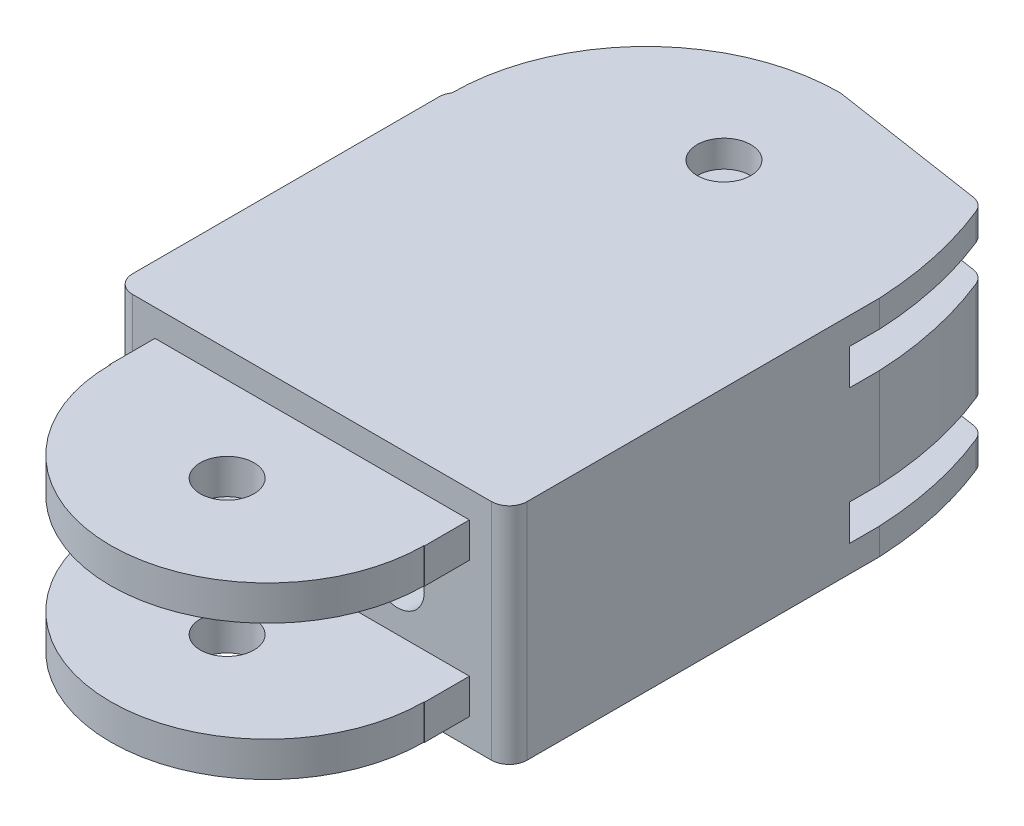
SolidWorks part; units mm, degrees
ref_plane "Front Plane" through (0, 0, 0) normal (0, 0, 1) x (1, 0, 0)
ref_plane "Top Plane" through (0, 0, 0) normal (0, 1, 0) x (1, 0, 0)
ref_plane "Right Plane" through (0, 0, 0) normal (1, 0, 0) x (0, 0, -1)
sketch "Sketch2" plane through (0, 0, 0) normal (0, 0, 1) x (1, 0, 0)
  line L0 (-24.2561, -24.0702) -> (-22.0061, -24.0702) construction
  line L1 (-24.2561, -17.8202) -> (-2.2017, -17.8202) construction
  line L2 (-24.2561, -17.8202) -> (-24.2561, -30.3202) construction
  line L3 (-24.2561, -30.3202) -> (-2.2017, -30.3202) construction
  line L4 (-2.2017, -17.8202) -> (-2.2017, -30.3202) construction
  line L5 (-2.2017, -24.0702) -> (-4.4517, -24.0702) construction
  line L6 (-22.0061, -24.0702) -> (-22.0061, -30.3202) construction
  line L7 (-4.4517, -24.0702) -> (-4.4517, -30.3202) construction
  line L8 (-24.2561, -17.8202) -> (-24.2561, -19.3148) construction
  line L9 (-24.2561, -19.3148) -> (-22.0061, -19.3148) construction
  line L10 (-2.2017, -17.8202) -> (-2.2017, -19.3148) construction
  line L11 (-2.2017, -19.3148) -> (-4.4517, -19.3148) construction
  line L12 (-2.2017, -30.3202) -> (-2.2017, -28.8202) construction
  line L13 (-2.2017, -28.8202) -> (-4.4517, -28.8202) construction
  line L14 (-24.2561, -30.3202) -> (-24.2561, -28.8202) construction
  line L15 (-24.2561, -28.8202) -> (-22.0061, -28.8202) construction
  line L17 (-22.0061, -28.8202) -> (-4.4517, -28.8202)
  line L18 (-22.0061, -28.8202) -> (-22.0061, -26.8702)
  line L19 (-22.0061, -26.8702) -> (-4.4517, -26.8702)
  line L20 (-4.4517, -28.8202) -> (-4.4517, -26.8702)
  line L21 (-22.0061, -28.8202) -> (-4.4517, -26.8702) construction
  line L22 (-22.0061, -26.8702) -> (-4.4517, -28.8202) construction
  line L23 (-22.0061, -19.3148) -> (-4.4517, -19.3148)
  line L24 (-22.0061, -19.3148) -> (-22.0061, -21.2648)
  line L25 (-22.0061, -21.2648) -> (-4.4517, -21.2648)
  line L26 (-4.4517, -19.3148) -> (-4.4517, -21.2648)
  line L27 (-22.0061, -19.3148) -> (-4.4517, -21.2648) construction
  line L28 (-22.0061, -21.2648) -> (-4.4517, -19.3148) construction
  point P19 (-13.2289, -27.8452)
  point P22 (-13.2289, -20.2898)
extrude "Boss-Extrude1" add sketch "Sketch2" along normal blind 8.75
sketch "Sketch3" plane through (0, -19.3148, 0) normal (0, 1, 0) x (1, 0, 0)
  line L0 (-4.4517, 0) -> (-22.0061, 0) construction
  line L1 (-4.4517, -8.75) -> (-22.0061, -8.75) construction
  arc A0 (-13.2289, -8.75) -> (-4.4789, 0) centre (-13.2289, 0) ccw
  arc A1 (-13.2289, -8.75) -> (-21.9789, 0) centre (-13.2289, 0) cw
  spline S0 degree 2 poles (-22.0061, -8.75) (-13.2289, -12.4735) (-4.4517, -8.75) knots 0 0 0 1 1 1
  spline S1 degree 2 poles (-21.9789, 0) (-25.927, -4.2429) (-22.0061, -8.75) knots 0 0 0 1 1 1
  spline S2 degree 2 poles (-4.4789, 0) (1.1383, -4.1517) (-4.4517, -8.75) knots 0 0 0 1 1 1
extrude "Cut-Extrude1" cut sketch "Sketch3" against normal through all contours S0 S2 A0 A1 S1
sketch "Sketch4" plane through (0, 0, 0) normal (0, 0, -1) x (-1, 0, 0)
  line L0 (22.0061, -19.3148) -> (24.2561, -19.3148) construction
  line L1 (22.0061, -19.3148) -> (4.4789, -19.3148) construction
  line L2 (22.0061, -19.3148) -> (22.0061, -28.8202) construction
  line L3 (22.0061, -28.8202) -> (4.4789, -28.8202) construction
  line L4 (4.4789, -19.3148) -> (4.4789, -28.8202) construction
  line L5 (22.0061, -19.3148) -> (4.4789, -28.8202) construction
  line L6 (22.0061, -28.8202) -> (4.4789, -19.3148) construction
  line L7 (24.2561, -19.3148) -> (24.2561, -17.8148) construction
  line L8 (4.4789, -28.8202) -> (2.2289, -28.8202) construction
  line L9 (2.2289, -28.8202) -> (2.2289, -30.3202) construction
  line L11 (24.2561, -17.8148) -> (2.2289, -17.8148)
  line L12 (24.2561, -17.8148) -> (24.2561, -30.3202)
  line L13 (24.2561, -30.3202) -> (2.2289, -30.3202)
  line L14 (2.2289, -17.8148) -> (2.2289, -30.3202)
  line L15 (24.2561, -17.8148) -> (2.2289, -30.3202) construction
  line L16 (24.2561, -30.3202) -> (2.2289, -17.8148) construction
  point P4 (13.2425, -24.0675)
  point P14 (13.2425, -24.0675)
extrude "Boss-Extrude2" add sketch "Sketch4" along normal blind 32 contours L12 L13 L14 L11
sketch "Sketch5" plane through (0, -19.3148, 0) normal (0, 1, 0) x (1, 0, 0)
  line L0 (-13.2289, -8.75) -> (-13.2289, -2.25) construction
  arc A0 (-21.9789, 0) -> (-4.4789, 0) centre (-13.2289, 0) ccw construction
  circle A1 centre (-13.2289, -2.25) radius 1.5
extrude "Cut-Extrude2" cut sketch "Sketch5" against normal blind 12 contours A1
sketch "Sketch6" plane through (0, 0, 0) normal (0, 0, 1) x (1, 0, 0)
  line L0 (-24.2561, -30.3202) -> (-2.2289, -30.3202)
  line L1 (-2.2289, -30.3202) -> (-2.2289, -17.8148)
  line L2 (-2.2289, -17.8148) -> (-24.2561, -17.8148)
  line L3 (-24.2561, -17.8148) -> (-24.2561, -30.3202)
  line L4 (-22.0061, -28.8202) -> (-4.4517, -28.8202)
  line L5 (-4.4517, -28.8202) -> (-4.4517, -26.8702)
  line L6 (-4.4517, -28.8202) -> (-4.4517, -26.8702) construction
  line L7 (-4.4517, -26.8702) -> (-22.0061, -26.8702)
  line L8 (-22.0061, -28.8202) -> (-22.0061, -26.8702)
  line L9 (-22.0061, -21.2648) -> (-22.0061, -19.3148)
  line L10 (-22.0061, -19.3148) -> (-4.4517, -19.3148)
  line L11 (-4.4517, -19.3148) -> (-4.4517, -21.2648)
  line L12 (-4.4517, -21.2648) -> (-22.0061, -21.2648)
extrude "Cut-Extrude3" cut sketch "Sketch6" against normal blind 2.5
sketch "Sketch7" plane through (0, -17.8148, 0) normal (0, 1, 0) x (1, 0, 0)
  line L0 (-13.2425, 32) -> (-13.2425, 25.5) construction
  line L1 (-24.2561, 32) -> (-2.2289, 32) construction
  line L2 (-13.2425, 25.5) -> (-13.2425, 21.1557) construction
  line L3 (-24.0869, 21.1557) -> (-24.2561, 21.1557)
  line L4 (-24.2561, 32) -> (-24.2561, 2.5) construction
  line L6 (-2.2289, 32) -> (-2.2289, 2.5) construction
  line L7 (-13.2425, 32) -> (-3.9485, 30.5853)
  circle A0 centre (-13.2425, 25.5) radius 1.5
  arc A1 (-13.2425, 32) -> (-24.0869, 21.1557) centre (-13.2425, 21.1557) ccw
  spline S0 degree 3 poles (-2.2289, 21.1557) (11.4715, 27.1897) (-11.7652, 53.4313) (-37.0079, 21.5236) (-24.2561, 21.1557) knots 0 0 0 0 0.520113 1 1 1 1
  spline S1 degree 2 poles (-3.9485, 30.5853) (-2.0071, 26.0937) (-2.2289, 21.1557) knots 0 0 0 1 1 1
  point P17 (-3.9485, 30.5853)
  point P19 (-2.742, 26.9228)
extrude "Cut-Extrude4" cut sketch "Sketch7" against normal blind 13
sketch "Sketch8" plane through (0, 0, -2.5) normal (0, 0, 1) x (1, 0, 0)
  line L0 (-24.2561, -24.0675) -> (-18.0111, -24.0675) construction
  line L1 (-24.2561, -17.8148) -> (-24.2561, -30.3202) construction
  line L2 (-2.2289, -24.0675) -> (-8.474, -24.0675) construction
  line L3 (-2.2289, -30.3202) -> (-2.2289, -17.8148) construction
  line L4 (-4.4517, -21.2648) -> (-4.4517, -24.0675) construction
  line L5 (-4.4517, -24.0675) -> (-8.474, -24.0675) construction
  circle A0 centre (-18.0111, -24.0675) radius 1.5
  circle A1 centre (-8.474, -24.0675) radius 1.5
extrude "Cut-Extrude5" cut sketch "Sketch8" against normal blind 28
fillet "Fillet3" radius 1 4 edges at (-24.2561, -24.0675, -2.5) (-24.2561, -24.0675, -21.1557) (-2.2289, -24.0675, -2.5) (-3.9485, -24.0675, -30.5853)
ref_plane "Plane4" through (0, 0, -32.5) normal (0, 0, 1) x (1, 0, 0)
sketch "Sketch9" plane through (0, 0, -32.5) normal (0, 0, 1) x (1, 0, 0)
  line L0 (-24.2561, -17.8148) -> (-24.2561, -19.3148) construction
  line L1 (-24.2561, -17.8148) -> (-2.2289, -17.8148) construction
  line L2 (-24.2561, -17.8148) -> (-24.2561, -30.3202) construction
  line L3 (-24.2561, -30.3202) -> (-2.2289, -30.3202) construction
  line L4 (-2.2289, -17.8148) -> (-2.2289, -30.3202) construction
  line L5 (-24.2561, -17.8148) -> (-2.2289, -30.3202) construction
  line L6 (-24.2561, -30.3202) -> (-2.2289, -17.8148) construction
  line L7 (-24.2561, -30.3202) -> (-24.2561, -28.8361) construction
  line L8 (-24.2561, -19.3148) -> (-2.2289, -19.3148)
  line L9 (-24.2561, -19.3148) -> (-24.2561, -21.3148)
  line L10 (-24.2561, -21.3148) -> (-2.2289, -21.3148)
  line L11 (-2.2289, -19.3148) -> (-2.2289, -21.3148)
  line L12 (-24.2561, -19.3148) -> (-2.2289, -21.3148) construction
  line L13 (-24.2561, -21.3148) -> (-2.2289, -19.3148) construction
  line L15 (-24.2561, -28.8361) -> (-2.2289, -28.8361)
  line L16 (-24.2561, -28.8361) -> (-24.2561, -26.8361)
  line L17 (-24.2561, -26.8361) -> (-2.2289, -26.8361)
  line L18 (-2.2289, -28.8361) -> (-2.2289, -26.8361)
  line L19 (-24.2561, -28.8361) -> (-2.2289, -26.8361) construction
  line L20 (-24.2561, -26.8361) -> (-2.2289, -28.8361) construction
  point P4 (-13.2425, -24.0675)
  point P8 (-13.2425, -20.3148)
  point P13 (-13.2425, -27.8361)
extrude "Cut-Extrude6" cut sketch "Sketch9" along normal blind 11
